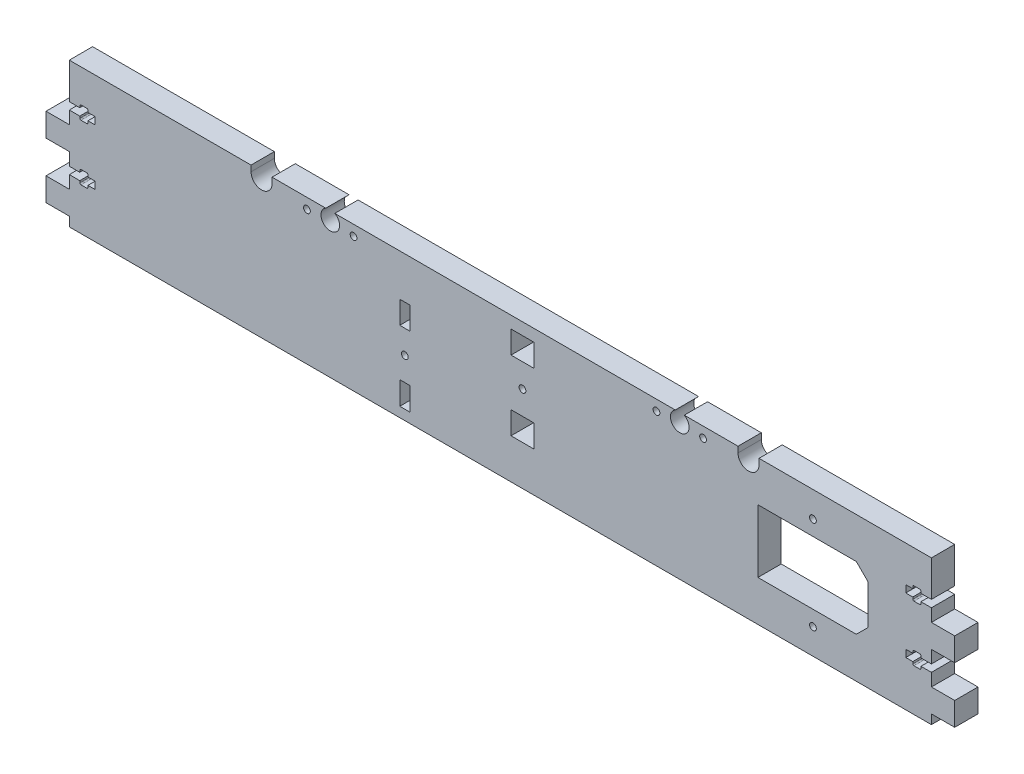
SolidWorks part; units mm, degrees
ref_plane "Front Plane" through (0, 0, 0) normal (0, 0, 1) x (1, 0, 0)
ref_plane "Top Plane" through (0, 0, 0) normal (0, 1, 0) x (1, 0, 0)
ref_plane "Right Plane" through (0, 0, 0) normal (1, 0, 0) x (0, 0, -1)
sketch "Sketch1" plane through (0, 0, 0) normal (0, 0, 1) x (1, 0, 0)
  line L0 (0, 0) -> (-185, 0)
  line L1 (-185, 0) -> (-185, -62) construction
  line L2 (0, -62) -> (-185, -62)
  line L3 (-185, -62) -> (-185, -58)
  line L4 (-185, -58) -> (-195, -58)
  line L5 (-195, -58) -> (-195, -48)
  line L6 (-195, -48) -> (-185, -48)
  line L7 (-185, -48) -> (-185, -34)
  line L8 (-185, -34) -> (-195, -34)
  line L9 (-195, -34) -> (-195, -24)
  line L10 (-195, -24) -> (-185, -24)
  line L11 (0, -62) -> (0, 0)
  line L12 (-185, -24) -> (-185, 0)
  line L13 (-195, -58) -> (-195, -24) construction
  line L14 (-195, -29) -> (-185, -29) construction
  line L15 (-195, -53) -> (-185, -53) construction
  dimension "D1" = 185
  dimension "D2" = 10
  dimension "D3" = 10
  dimension "D4" = 10
  dimension "D5" = 24
  dimension "D6" = 29
  dimension "D7" = 62
extrude "MainBody" add sketch "Sketch1" along normal blind 10
sketch "Sketch3" plane through (0, 0, 10) normal (0, 0, 1) x (1, 0, 0)
  line L0 (-185, -17) -> (-174, -17) construction
  line L1 (-185, 0) -> (-185, -24) construction
  line L2 (-185, -18.55) -> (-180.5, -18.55)
  line L3 (-180.5, -18.55) -> (-180.5, -19.35)
  line L4 (-180, -19.85) -> (-177.5, -19.85)
  line L5 (-177, -19.35) -> (-177, -18.55)
  line L6 (-177, -18.55) -> (-174, -18.55)
  line L7 (-174, -18.55) -> (-174, -15.45)
  line L8 (-180.5, -18.55) -> (-177, -18.55) construction
  line L9 (-195, -24) -> (-195, -34) construction
  line L10 (-180.5, -15.45) -> (-177, -15.45) construction
  line L11 (-177, -15.45) -> (-174, -15.45)
  line L12 (-177, -14.65) -> (-177, -15.45)
  line L13 (-180, -14.15) -> (-177.5, -14.15)
  line L14 (-180.5, -15.45) -> (-180.5, -14.65)
  line L15 (-185, -15.45) -> (-180.5, -15.45)
  line L16 (-185, -18.55) -> (-185, -15.45)
  line L17 (-185, -24) -> (-185, -34) construction
  line L19 (-195, -24) -> (-195, -34) construction
  line L20 (-195, -29) -> (-185, -29) construction
  line L21 (-180.5, -42.55) -> (-177, -42.55) construction
  line L22 (-180.5, -39.45) -> (-177, -39.45) construction
  line L23 (-185, -41) -> (-174, -41) construction
  line L24 (-185, -39.45) -> (-185, -42.55)
  line L25 (-185, -42.55) -> (-180.5, -42.55)
  line L26 (-180.5, -42.55) -> (-180.5, -43.35)
  line L27 (-180, -43.85) -> (-177.5, -43.85)
  line L28 (-177, -43.35) -> (-177, -42.55)
  line L29 (-177, -42.55) -> (-174, -42.55)
  line L30 (-174, -39.45) -> (-174, -42.55)
  line L31 (-177, -39.45) -> (-174, -39.45)
  line L32 (-177, -38.65) -> (-177, -39.45)
  line L33 (-180, -38.15) -> (-177.5, -38.15)
  line L34 (-180.5, -39.45) -> (-180.5, -38.65)
  line L35 (-185, -39.45) -> (-180.5, -39.45)
  line L36 (-180.5, -15.45) -> (-177, -15.45) construction
  arc A0 (-177.5, -19.85) -> (-177, -19.35) centre (-177.5, -19.35) ccw
  arc A1 (-180.5, -19.35) -> (-180, -19.85) centre (-180, -19.35) ccw
  arc A2 (-180.5, -14.65) -> (-180, -14.15) centre (-180, -14.65) cw
  arc A3 (-177.5, -14.15) -> (-177, -14.65) centre (-177.5, -14.65) cw
  arc A4 (-177.5, -43.85) -> (-177, -43.35) centre (-177.5, -43.35) ccw
  arc A5 (-180.5, -43.35) -> (-180, -43.85) centre (-180, -43.35) ccw
  arc A6 (-180.5, -38.65) -> (-180, -38.15) centre (-180, -38.65) cw
  arc A7 (-177.5, -38.15) -> (-177, -38.65) centre (-177.5, -38.65) cw
  point P6 (-195, -29)
  point P15 (-177, -19.85)
  point P18 (-180.5, -19.85)
  point P29 (-180.5, -14.15)
  point P30 (-177, -14.15)
  point P62 (-177, -43.85)
  point P63 (-180.5, -43.85)
  point P64 (-180.5, -38.15)
  point P65 (-177, -38.15)
  dimension "D2" = 8
  dimension "D7" = 0.5
  dimension "D1" = 11
  dimension "D3" = 1.55
  dimension "D4" = 2.85
  dimension "D5" = 12
  dimension "D6" = 3.5
extrude "ScrewCutouts" cut sketch "Sketch3" against normal through all
mirror "Mirror1" about plane through (0, 0, 0) normal (1, 0, 0) of "ScrewCutouts", "MainBody"
sketch "Sketch2" plane through (0, 0, 10) normal (0, 0, 1) x (1, 0, 0)
  line L0 (0, 0) -> (0, -62) construction
  line L1 (-185, -62) -> (185, -62) construction
  line L2 (2, 0) -> (2, -62) construction
  line L3 (185, 0) -> (-185, 0) construction
  line L4 (-63, -4.5) -> (-83, -4.5) construction
  line L5 (-73, -7.5) -> (-73, 0.5) construction
  line L6 (77, -7.5) -> (77, 0.5) construction
  line L7 (67, -4.5) -> (87, -4.5) construction
  circle A0 centre (-73, -3.5) radius 4
  circle A1 centre (-83, -4.5) radius 1.45
  circle A2 centre (-63, -4.5) radius 1.45
  circle A3 centre (67, -4.5) radius 1.45
  circle A4 centre (87, -4.5) radius 1.45
  circle A5 centre (77, -3.5) radius 4
  dimension "D1" = 2.9
  dimension "D2" = 8
  dimension "D4" = 3.5
  dimension "D5" = 75
  dimension "D6" = 2
  dimension "D3" = 10
  dimension "D7" = 1
extrude "RodCutouts" cut sketch "Sketch2" against normal through all
sketch "Sketch4" plane through (0, 0, 10) normal (0, 0, 1) x (1, 0, 0)
  line L0 (77, -3.5) -> (-73, -3.5) construction
  line L1 (2, -3.5) -> (2, -62) construction
  line L2 (-185, -62) -> (185, -62) construction
  line L3 (9.5, -44.85) -> (9.5, -5.15) construction
  line L4 (75.0635, 0) -> (-71.0635, 0) construction
  line L5 (9.5, -10) -> (9.5, -40) construction
  line L6 (4.575, -5.15) -> (14.425, -5.15)
  line L7 (4.575, -5.15) -> (4.575, -14.85)
  line L8 (4.575, -14.85) -> (14.425, -14.85)
  line L9 (14.425, -5.15) -> (14.425, -14.85)
  line L10 (4.575, -5.15) -> (14.425, -14.85) construction
  line L11 (4.575, -14.85) -> (14.425, -5.15) construction
  line L12 (4.575, -35.15) -> (14.425, -35.15)
  line L13 (4.575, -35.15) -> (4.575, -44.85)
  line L14 (4.575, -44.85) -> (14.425, -44.85)
  line L15 (14.425, -35.15) -> (14.425, -44.85)
  line L16 (4.575, -35.15) -> (14.425, -44.85) construction
  line L17 (4.575, -44.85) -> (14.425, -35.15) construction
  circle A0 centre (9.5, -25) radius 1.45
  point P12 (9.5, -10)
  point P17 (9.5, -40)
  dimension "D8" = 2.9
  dimension "D1" = 9.85
  dimension "D2" = 9.7
  dimension "D3" = 9.85
  dimension "D4" = 9.7
  dimension "D5" = 30
  dimension "D6" = 10
  dimension "D7" = 7.5
extrude "Cut-Extrude3" cut sketch "Sketch4" against normal through all
sketch "Sketch5" plane through (0, 0, 10) normal (0, 0, 1) x (1, 0, 0)
  line L0 (-41, 0) -> (-41, -62) construction
  line L1 (-74.9365, 0) -> (-185, 0) construction
  line L2 (-185, -62) -> (185, -62) construction
  line L3 (-43.175, -27.65) -> (-43.175, -47.85) construction
  line L4 (-43.175, -17.95) -> (-38.825, -17.95)
  line L5 (-43.175, -17.95) -> (-43.175, -27.65)
  line L6 (-43.175, -27.65) -> (-38.825, -27.65)
  line L7 (-38.825, -17.95) -> (-38.825, -27.65)
  line L8 (-43.175, -17.95) -> (-38.825, -27.65) construction
  line L9 (-43.175, -27.65) -> (-38.825, -17.95) construction
  line L10 (-43.175, -47.85) -> (-38.825, -47.85)
  line L11 (-43.175, -47.85) -> (-43.175, -57.75)
  line L12 (-43.175, -57.75) -> (-38.825, -57.75)
  line L13 (-38.825, -47.85) -> (-38.825, -57.75)
  line L14 (-43.175, -47.85) -> (-38.825, -57.75) construction
  line L15 (-43.175, -57.75) -> (-38.825, -47.85) construction
  line L16 (-38.825, -47.85) -> (-38.825, -27.65) construction
  line L17 (-43.175, -37.75) -> (-38.825, -37.75) construction
  line L18 (-73, -3.5) -> (77, -3.5) construction
  line L19 (2, -3.5) -> (2, -62) construction
  line L20 (2, -32.75) -> (-195, -32.75) construction
  line L21 (-195, -24) -> (-195, -34) construction
  line L22 (-34.625, 8.9944) -> (-34.625, 5) construction
  line L23 (75.0635, 0) -> (-71.0635, 0) construction
  line L24 (-31.425, 8.9944) -> (-31.425, 5)
  line L25 (-37.825, 8.9944) -> (-37.825, 5)
  circle A0 centre (-41, -37.75) radius 1.45
  arc A1 (-31.425, 8.9944) -> (-37.825, 8.9944) centre (-34.625, 8.9944) ccw
  arc A2 (-37.825, 5) -> (-31.425, 5) centre (-34.625, 5) ccw
  point P6 (-41, -22.8)
  point P11 (-41, -52.8)
  point P34 (-34.625, 6.9972)
  dimension "D4" = 9.7
  dimension "D5" = 30
  dimension "D6" = 2.9
  dimension "D9" = 3.2
  dimension "D1" = 4.35
  dimension "D2" = 0
  dimension "D3" = 9.9
  dimension "D7" = 43
  dimension "D8" = 5
  dimension "D10" = 5
  dimension "D11" = 1
extrude "EndstopHolder" cut sketch "Sketch5" against normal through all
sketch "Sketch6" plane through (0, 0, 10) normal (0, 0, 1) x (1, 0, 0)
  line L0 (-43.175, -47.85) -> (-43.175, -27.65) construction
  line L1 (-42.35, -47.85) -> (-30.825, -47.85) construction
  line L3 (-30.825, -53.85) -> (-30.825, -41.85) construction
  line L4 (-32.825, -53.85) -> (-32.825, -41.85)
  line L5 (-28.825, -53.85) -> (-28.825, -41.85)
  line L6 (-38.825, -47.85) -> (-43.175, -47.85) construction
  line L7 (-38.825, -57.75) -> (-38.825, -47.85) construction
  arc A0 (-32.825, -53.85) -> (-28.825, -53.85) centre (-30.825, -53.85) ccw
  arc A1 (-28.825, -41.85) -> (-32.825, -41.85) centre (-30.825, -41.85) ccw
  point P10 (-30.825, -47.85)
  dimension "D1" = 2
  dimension "D2" = 12
  dimension "D3" = 8
  dimension "D4" = 0
extrude "EndstopWires" [suppressed] cut sketch "Sketch6" against normal through all
sketch "Sketch7" plane through (0, 0, 10) normal (0, 0, 1) x (1, 0, 0)
  line L0 (-73, -3.5) -> (77, -3.5) construction
  line L1 (2, -3.5) -> (2, -62) construction
  line L3 (-102.5, 0) -> (-102.5, -2.5) construction
  line L4 (-74.9365, 0) -> (-185, 0) construction
  line L5 (-98, 0) -> (-98, -2.5)
  line L6 (-107, 0) -> (-107, -2.5)
  line L7 (106.5, 0) -> (106.5, -2.5) construction
  line L8 (102, 0) -> (102, -2.5)
  line L9 (111, 0) -> (111, -2.5)
  line L10 (-185, -62) -> (185, -62) construction
  arc A0 (-98, 0) -> (-107, 0) centre (-102.5, 0) ccw
  arc A1 (-107, -2.5) -> (-98, -2.5) centre (-102.5, -2.5) ccw
  arc A2 (102, 0) -> (111, 0) centre (106.5, 0) cw
  arc A3 (111, -2.5) -> (102, -2.5) centre (106.5, -2.5) cw
  point P12 (-102.5, -1.25)
  point P19 (106.5, -1.25)
  dimension "D3" = 4.5
  dimension "D1" = 2.5
  dimension "D2" = 104.5
extrude "Cut-Extrude4" cut sketch "Sketch7" against normal through all
ref_plane "Plane1" through (0, -31, 0) normal (0, 1, 0) x (1, 0, 0)
sketch "Sketch8" plane through (0, 0, 10) normal (0, 0, 1) x (1, 0, 0)
  line L0 (133.7748, 0) -> (133.7748, -62) construction
  line L1 (185, 0) -> (111, 0) construction
  line L2 (-185, -62) -> (185, -62) construction
  line L3 (132.2469, -17.485) -> (110.5361, -17.485) construction
  line L4 (151.9576, -17.485) -> (112.5361, -17.485) construction
  line L5 (110.5361, -17.485) -> (110.5361, -44.515)
  line L6 (110.5361, -19.485) -> (110.5361, -42.515) construction
  line L7 (112.5361, -44.515) -> (151.9576, -44.515) construction
  line L8 (110.5361, -44.515) -> (152.7861, -44.515)
  line L9 (152.7861, -44.515) -> (157.7861, -39.515)
  line L10 (157.7861, -39.515) -> (157.7861, -22.485)
  line L11 (157.7861, -22.485) -> (152.7861, -17.485)
  line L12 (152.7861, -17.485) -> (110.5361, -17.485)
  line L13 (157.7861, -38.6866) -> (157.7861, -23.3134) construction
  line L14 (157.2003, -21.8992) -> (153.3719, -18.0708) construction
  line L15 (153.3719, -43.9292) -> (157.2003, -40.1008) construction
extrude "Cut-Extrude5" cut sketch "Sketch8" against normal through all
sketch "Sketch9" plane through (0, 0, 0) normal (0, 0, -1) x (-1, 0, 0)
  line L0 (-105.0611, -31) -> (-163.2611, -31) construction
  line L1 (-105.0611, -43.5977) -> (-105.0611, -18.4023) construction
  line L2 (-163.2611, -18.4023) -> (-163.2611, -43.5977) construction
  circle A0 centre (-134.1611, -11) radius 1.45
  circle A1 centre (-134.1611, -11) radius 1.6 construction
  circle A2 centre (-134.1611, -51) radius 1.45
  dimension "D1" = 2.9
extrude "Cut-Extrude6" cut sketch "Sketch9" against normal through all
equation "\"Y-ROD-SPACING\"=75"
equation "\"D5@Sketch2\"=\"Y-ROD-SPACING\""
equation "\"Y-BED-OFFSET\"=2"
equation "\"D6@Sketch2\"=\"Y-BED-OFFSET\""
equation "\"T-SLOT-NUT-FILLET-RADIUS\"=0.5"
equation "\"D7@Sketch3\"=\"T-SLOT-NUT-FILLET-RADIUS\""
equation "\"T-SLOT-SCREW-SHAFT-RADIUS\"=1.55"
equation "\"D3@Sketch3\"=\"T-SLOT-SCREW-SHAFT-RADIUS\""
equation "\"T-SLOT-SCREW-SHAFT-CUTOUT-LENGTH\"=11"
equation "\"D1@Sketch3\"=\"T-SLOT-SCREW-SHAFT-CUTOUT-LENGTH\""
equation "\"T-SLOT-NUT-DEPTH\"=3.5"
equation "\"D6@Sketch3\"=\"T-SLOT-NUT-DEPTH\""
equation "\"T-SLOT-NUT-WIDTH\"=2.85"
equation "\"D4@Sketch3\"=\"T-SLOT-NUT-WIDTH\""
equation "\"T-SLOT-NUT-END-DISTANCE\"=8"
equation "\"D2@Sketch3\"=\"T-SLOT-NUT-END-DISTANCE\""
equation "\"ACRYLIC-TAB-CUTOUT-SIZE\"=\"ACRYLIC-THICKNESS\"+\"ACRYLIC-TAB-TOLERANCE\"*2"
equation "\"D1@Sketch4\"=\"ACRYLIC-THICKNESS\"-\"KERF\"*2"
equation "\"D2@Sketch4\"=\"ACRYLIC-TAB-WIDTH\"-\"KERF\"*4"
equation "\"D3@Sketch4\"=\"ACRYLIC-THICKNESS\"-\"KERF\"*2"
equation "\"D4@Sketch4\"=\"ACRYLIC-TAB-WIDTH\"-\"KERF\"*4"
equation "\"ACRYLIC-M3-HOLE\"=2.9"
equation "\"D8@Sketch4\"=\"ACRYLIC-M3-HOLE\""
equation "\"Y-BED-ROD-INSET\"=3.5"
equation "\"D1@Sketch2\"=\"ACRYLIC-M3-HOLE\""
equation "\"D4@Sketch2\"=\"Y-BED-ROD-INSET\""
equation "\"SMOOTHROD-CAP-SCREW-DISTANCE\"=20"
equation "\"D3@Sketch2\"=\"SMOOTHROD-CAP-SCREW-DISTANCE\"/2"
equation "\"ACRYLIC-TAB-WIDTH\"=\"ACRYLIC-THICKNESS\""
equation "\"FRAME-WIDTH-INNER\"=370"
equation "\"D2@Sketch1\"=\"ACRYLIC-TAB-WIDTH\""
equation "\"D3@Sketch1\"=\"ACRYLIC-TAB-WIDTH\""
equation "\"D4@Sketch1\"=\"ACRYLIC-TAB-WIDTH\""
equation "\"D1@Sketch1\"=\"FRAME-WIDTH-INNER\"/2"
equation "\"X-ROD-SPACING\"=45"
equation "\"Z-ROD-SPACING\"=17.5"
equation "\"ACRYLIC-THICKNESS\"=10"
equation "\"ACRYLIC-THICKNESS2\"=4.5"
equation "\"NEMA17-HOLE-SPACING\"=31"
equation "\"NEMA17-CENTRAL-CUTOUT\"=22.5"
equation "\"Z-BRACKET-REACH\"=57"
equation "\"TOP-BRACKET-SPACING\"=40"
equation "\"SMOOTHROD-X-LENGTH\"=350"
equation "\"SMOOTHROD-Y-LENGTH\"=350"
equation "\"SMOOTHROD-Z-LENGTH\"=350"
equation "\"SMOOTHROD-TIGHTENING-HEADROOM\"=.25"
equation "\"LEADSCREW-Z-LENGTH\"=300"
equation "\"SCREW-LENGTH-FRAME\"=\"ACRYLIC-THICKNESS\" + 10"
equation "\"SCREW-HEAD-RADIUS\"=6"
equation "\"PRINTED-X-SMOOTHROD-DIAMETER\"=8.8"
equation "\"PRINTED-X-SMOOTHROD-CUTOUT\"=10"
equation "\"PRINTED-X-BASE-HEIGHT\"=10"
equation "\"PRINTED-LM8UU-CUTOUT-SIZE\"=15.5"
equation "\"PRINTED-LM8UU-CUTOUT-LENGTH\"=24.5"
equation "\"PRINTED-X-IDLER-HEIGHT\"=16"
equation "\"PSU-MOUNTING-WIDTH\"=95"
equation "\"PSU-MOUNTING-HEIGHT\"=177"
equation "\"D1@MainBody\"=\"ACRYLIC-THICKNESS\""
equation "\"D1@Sketch5\"=\"ACRYLIC-THICKNESS2\"-\"KERF\"*2"
equation "\"D3@Sketch5\"=\"ACRYLIC-TAB-CUTOUT-SIZE\""
equation "\"D4@Sketch5\"=\"ACRYLIC-TAB-WIDTH\"-\"KERF\"*4"
equation "\"D6@Sketch5\"=\"ACRYLIC-M3-HOLE\""
equation "\"Y-BED-SCREW-SPACING\"=209"
equation "\"Y-BED-SCREW-CUTOUT-SLOT-HEIGHT\"=2.5"
equation "\"Z-ROD-INSET\"=13.5"
equation "\"Y-BELT-TO-ROD-DISTANCE\"=20"
equation "\"SPOOL-HOLDER-ROD-SPACING\"=150"
equation "\"D1@Sketch7\"=\"Y-BED-SCREW-CUTOUT-SLOT-HEIGHT\""
equation "\"D2@Sketch7\"=\"Y-BED-SCREW-SPACING\"/2"
equation "\"ACRYLIC-TAB-TOLERANCE\"=-.05"
equation "\"SCREW-LENGTH-MOTOR\"=\"ACRYLIC-THICKNESS\" + 5"
equation "\"SCREW-LENGTH-EXTRUDER\"=28"
equation "\"ACRYLIC-X-CARRIAGE-WIDTH\"=55"
equation "\"ACRYLIC-X-CARRIAGE-HEIGHT\"=75"
equation "\"ACRYLIC-X-CARRIAGE-LM8UU-CUTOUT-WIDTH\"=24.25"
equation "\"ACRYLIC-X-CARRIAGE-SCREW-SPACING-X\"=15"
equation "\"ACRYLIC-X-CARRIAGE-SCREW-SPACING-Y\"=33"
equation "\"ACRYLIC-X-CARRIAGE-CENTER-TAB-SPACING\"=14"
equation "\"ACRYLIC-X-CARRIAGE-EXTRUDER-OFFSET\"=26"
equation "\"ACRYLIC-X-CARRIAGE-EXTRUDER-ANGLE\"=90"
equation "\"ACRYLIC-X-CARRIAGE-EXTRUDER-SHELF-DEPTH\"=\"ACRYLIC-X-CARRIAGE-EXTRUDER-OFFSET\" + 28"
equation "\"ACRYLIC-X-CARRIAGE-EXTRUDER-BRACE-SPACING\"=23"
equation "\"ACRYLIC-X-CARRIAGE-EXTRUDER-BRACE-TAB-OFFSET\"=20"
equation "\"ACRYLIC-X-CARRIAGE-EXTRUDER-BRACE-HEIGHT\"=35"
equation "\"ACRYLIC-X-CARRIAGE-EXTRUDER-BRACE-SCREW-SPACING\"=22"
equation "\"PRINTED-M3-HOLE\"=3.5"
equation "\"ACRYLIC-X-CARRIAGE-LM8UU-CUTOUT-HEIGHT\"=11.0"
equation "\"ACRYLIC-X-CARRIAGE-DUAL-WIDTH-MULTIPLIER\"=1.65"
equation "\"ACRYLIC-X-CARRIAGE-DUAL-HOTEND-SPACING\"=42"
equation "\"ACRYLIC-X-CARRIAGE-DUAL-WIDTH\"=75"
equation "\"ACRYLIC-X-CARRIAGE-DUAL-HOTEND-SEPARATION\"=36"
equation "\"ACRYLIC-X-CARRIAGE-DUAL-MOUNT-PLATE-DEPTH\"=75"
equation "\"ACRYLIC-X-CARRIAGE-DUAL-MOUNT-BRACE-WIDTH\"=33"
equation "\"ACRYLIC-X-CARRIAGE-DUAL-MOUNT-SCREW-WIDTH\"=40"
equation "\"BLOWER-FAN-WIDTH\"=15"
equation "\"KERF\"=0.075"
equation "\"PRINTED-M3-NUT-AF\"=6.25"
equation "\"ACRYLIC-X-CARRIAGE-DUAL-FAN-OFFSET\"=52"
equation "\"ACRYLIC-X-CARRIAGE-DUAL-FAN-HEIGHT\"=20"
equation "\"D1@Sketch9\"=\"ACRYLIC-M3-HOLE\""
